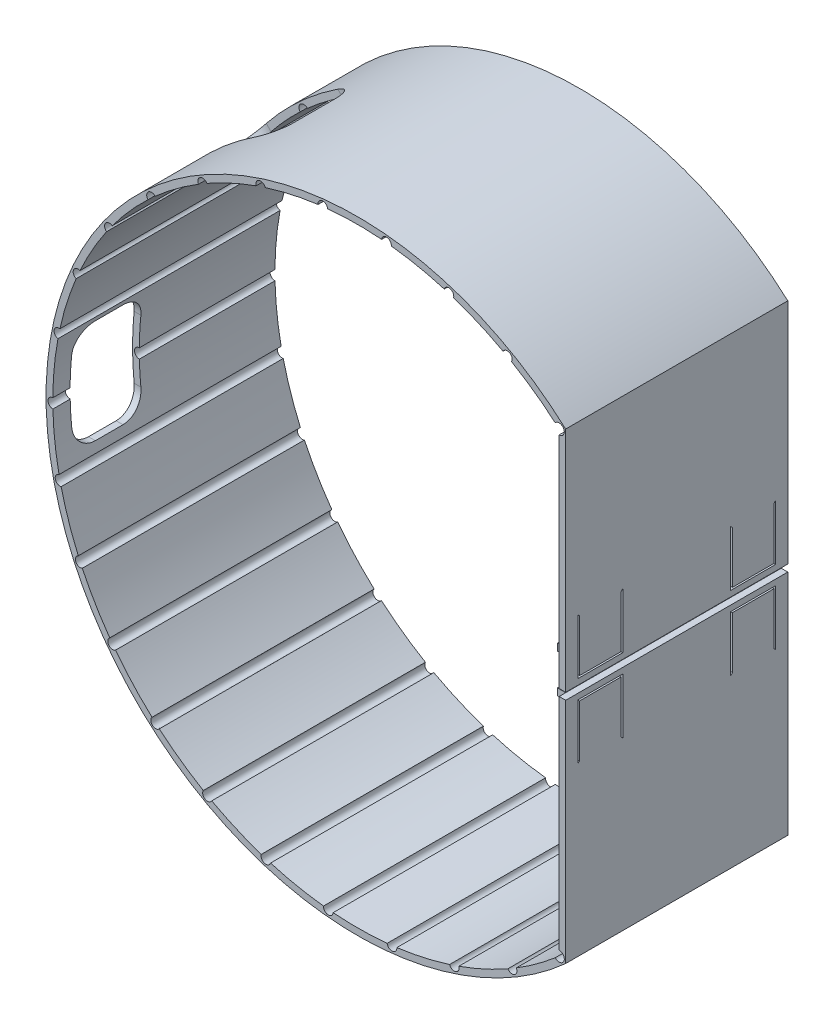
SolidWorks part; units mm, degrees
ref_plane "Front Plane" through (0, 0, 0) normal (1, 0, 0) x (0, 1, 0)
ref_plane "Top Plane" through (0, 0, 0) normal (0, 0, 1) x (0, 1, 0)
ref_plane "Right Plane" through (0, 0, 0) normal (0, 1, 0) x (-1, 0, 0)
sketch "Sketch1" plane through (0, 0, 0) normal (0, 0, 1) x (0, 1, 0)
  line L0 (-66.9026, -60.2) -> (-1, -60.2)
  line L1 (-65.9842, -58.3) -> (-1, -58.3)
  line L2 (-1, -60.2) -> (-1, -58.3)
  line L3 (1, -60.2) -> (1, -58.3)
  line L4 (1, -60.2) -> (66.9026, -60.2)
  line L5 (1, -58.3) -> (65.9842, -58.3)
  arc A0 (66.9026, -60.2) -> (-66.9026, -60.2) centre (0, 0) ccw
  arc A1 (65.9842, -58.3) -> (-65.9842, -58.3) centre (0, 0) ccw
  dimension "D1" = 180
  dimension "D2" = 176.1
  dimension "D3" = 60.2
  dimension "D4" = 1.9
  dimension "D5" = 1
  dimension "D6" = 1
extrude "Boss-Extrude1" add sketch "Sketch1" along normal blind 64.2
sketch "Sketch2" plane through (0, 0, 0) normal (1, 0, 0) x (0, 1, 0)
  line L0 (0, 67.3305) -> (0, -7.6543) construction
ref_plane "Plane1" through (0, 0, 0) normal (0.7071, -0.7071, 0) x (0, 0, -1)
sketch "Sketch3" plane through (0, 0, 0) normal (0.7071, -0.7071, 0) x (0, 0, -1)
  line L0 (-64.2, 87.8822) -> (-64.2, -88.05) construction
  line L1 (-44.2, -16.05) -> (-20.2, -16.05)
  line L2 (-44.2, -16.05) -> (-44.2, 23.95)
  line L3 (-44.2, 23.95) -> (-20.2, 23.95)
  line L4 (-20.2, -16.05) -> (-20.2, 23.95)
  line L6 (-64.2, -88.05) -> (0, -88.05) construction
  dimension "D1" = 40
  dimension "D2" = 24
  dimension "D3" = 20
  dimension "D4" = 72
extrude "Cut-Extrude1" cut sketch "Sketch3" against normal blind 120.2
sketch "Sketch4" plane through (0, 0, 0) normal (1, 0, 0) x (0, 1, 0)
  line L0 (0, 200067.3305) -> (0, -200007.6543) construction
  line L1 (-15, 59.2) -> (15, 59.2)
  line L2 (-15, 59.2) -> (-15, 39.2)
  line L3 (-15, 39.2) -> (15, 39.2)
  line L4 (15, 59.2) -> (15, 39.2)
  line L5 (90, 64.2) -> (-90, 64.2) construction
  dimension "D1" = 15
  dimension "D2" = 15
  dimension "D3" = 20
  dimension "D4" = 5
extrude "Cut-Extrude2" cut sketch "Sketch4" against normal blind 120.2
fillet "Fillet1" radius 6 8 edges at (-43.6939, 77.5643, 44.2) (-73.2676, 50.5695, 44.2) (-73.2676, 50.5695, 20.2) (-43.6939, 77.5643, 20.2) (-87.7521, 15, 39.2) (-87.7521, -15, 39.2) (-87.7521, -15, 59.2) (-87.7521, 15, 59.2)
sketch "Sketch5" plane through (58.3, 0, 0) normal (-1, 0, 0) x (0, -1, 0)
  line L0 (90, 64.2) -> (-90, 64.2) construction
  line L5 (-6.5842, 58.7) -> (-4.5842, 58.7)
  line L6 (-6.5842, 58.7) -> (-6.5842, 49.7)
  line L7 (-6.5842, 49.7) -> (-4.5842, 49.7)
  line L8 (-4.5842, 58.7) -> (-4.5842, 49.7)
  line L9 (-6.5842, 58.7) -> (-4.5842, 49.7) construction
  line L10 (-6.5842, 49.7) -> (-4.5842, 58.7) construction
  line L11 (-65.9842, 64.2) -> (-65.9842, 0) construction
  line L12 (-65.9842, 32.1) -> (65.9842, 32.1) construction
  line L13 (65.9842, 64.2) -> (65.9842, 0) construction
  point P0 (-5.5842, 54.2)
  dimension "D1" = 2
  dimension "D2" = 9
  dimension "D3" = 10
  dimension "D4" = 60.4
extrude "Boss-Extrude2" add sketch "Sketch5" along normal blind 6
sketch "Sketch6" plane through (0, 0, 58.7) normal (0, 0, 1) x (1, 0, 0)
  line L0 (58.3, 6.5842) -> (56.1, 6.5842) construction
  line L1 (52.3, 6.5842) -> (58.3, 6.5842) construction
  line L2 (56.1, 6.5842) -> (56.1, 7.5842)
  line L3 (52.3, 6.5842) -> (56.1, 7.5842)
  line L4 (52.3, 6.5842) -> (56.1, 6.5842)
  dimension "D1" = 1
extrude "Boss-Extrude3" add sketch "Sketch6" against normal blind 9
sketch "Sketch7" plane through (58.3, 0, 0) normal (-1, 0, 0) x (0, -1, 0)
  line L0 (-4.5842, 58.7) -> (-6.5842, 58.7) construction
  line L1 (-18.1626, 60.2) -> (-3.1626, 60.2)
  line L3 (-18.1626, 48.2) -> (-3.1626, 48.2)
  line L4 (-3.1626, 60.2) -> (-3.1626, 48.2)
  line L5 (-18.1626, 60.2) -> (-3.1626, 48.2) construction
  line L6 (-18.1626, 48.2) -> (-3.1626, 60.2) construction
  line L8 (-2.6626, 60.7) -> (-18.6626, 60.7)
  line L9 (-2.6626, 60.7) -> (-2.6626, 47.7)
  line L10 (-2.6626, 47.7) -> (-18.6626, 47.7)
  line L12 (-2.6626, 60.7) -> (-18.6626, 47.7) construction
  line L13 (-2.6626, 47.7) -> (-18.6626, 60.7) construction
  line L14 (-18.1626, 60.2) -> (-18.6626, 60.7)
  line L15 (-18.1626, 48.2) -> (-18.6626, 47.7)
  point P0 (-10.6626, 54.2)
  point P7 (-10.6626, 54.2)
  dimension "D1" = 12
  dimension "D2" = 15
  dimension "D3" = 1.5
  dimension "D4" = 0.5
  dimension "D5" = 0.5
extrude "Cut-Extrude3" cut sketch "Sketch7" against normal blind 9
sketch "Sketch8" plane through (58.3, 0, 0) normal (-1, 0, 0) x (0, -1, 0)
  line L0 (0, 74.2736) -> (0, -25.5173) construction
  line L1 (0, 200067.3305) -> (0, -200007.6543) construction
  line L2 (-65.9842, 32.1) -> (101.8942, 32.1) construction
  line L3 (-65.9842, 64.2) -> (-65.9842, 0) construction
ref_plane "Plane2" through (0, 0, 0) normal (0, 1, 0) x (-1, 0, 0)
ref_plane "Plane3" through (0, 0, 32.1) normal (0, 0, 1) x (0, -1, 0)
mirror "Mirror1" about plane through (0, 0, 0) normal (0, 1, 0) of "Cut-Extrude3", "Boss-Extrude3", "Boss-Extrude2"
mirror "Mirror2" about plane through (0, 0, 32.1) normal (0, 0, 1) of "Mirror1", "Cut-Extrude3", "Boss-Extrude3", "Boss-Extrude2"
sketch "Sketch9" plane through (0, 0, 64.2) normal (0, 0, 1) x (1, 0, 0)
  circle A0 centre (-88.0464, -0.7976) radius 1.4
  arc A1 (58.3, 65.9842) -> (58.3, -65.9842) centre (0, 0) ccw construction
  circle A2 centre (-86.2882, 17.5257) radius 1.4
  circle A3 centre (-80.7588, 35.083) radius 1.4
  circle A4 centre (-71.6998, 51.1071) radius 1.4
  circle A5 centre (-59.5073, 64.8975) radius 1.4
  circle A6 centre (-44.7139, 75.8516) radius 1.4
  circle A7 centre (-27.9664, 83.4906) radius 1.4
  circle A8 centre (-9.9966, 87.4807) radius 1.4
  circle A9 centre (8.4101, 87.6474) radius 1.4
  circle A10 centre (26.4493, 83.9836) radius 1.4
  circle A11 centre (43.3325, 76.6492) radius 1.4
  circle A21 centre (44.7139, -75.8516) radius 1.4
  circle A22 centre (27.9664, -83.4906) radius 1.4
  circle A23 centre (9.9966, -87.4807) radius 1.4
  circle A24 centre (-8.4101, -87.6474) radius 1.4
  circle A25 centre (-26.4493, -83.9836) radius 1.4
  circle A26 centre (-43.3325, -76.6492) radius 1.4
  circle A27 centre (-58.3218, -65.9649) radius 1.4
  circle A28 centre (-70.7622, -52.3976) radius 1.4
  circle A29 centre (-80.11, -36.5403) radius 1.4
  circle A30 centre (-85.9565, -19.086) radius 1.4
  circle A31 centre (58.3, -65.9842) radius 1.5
  circle A32 centre (58.3, 65.9842) radius 1.5
  point P66 (0, 0)
  dimension "D1" = 2.8
extrude "Cut-Extrude5" cut sketch "Sketch9" against normal blind 100
